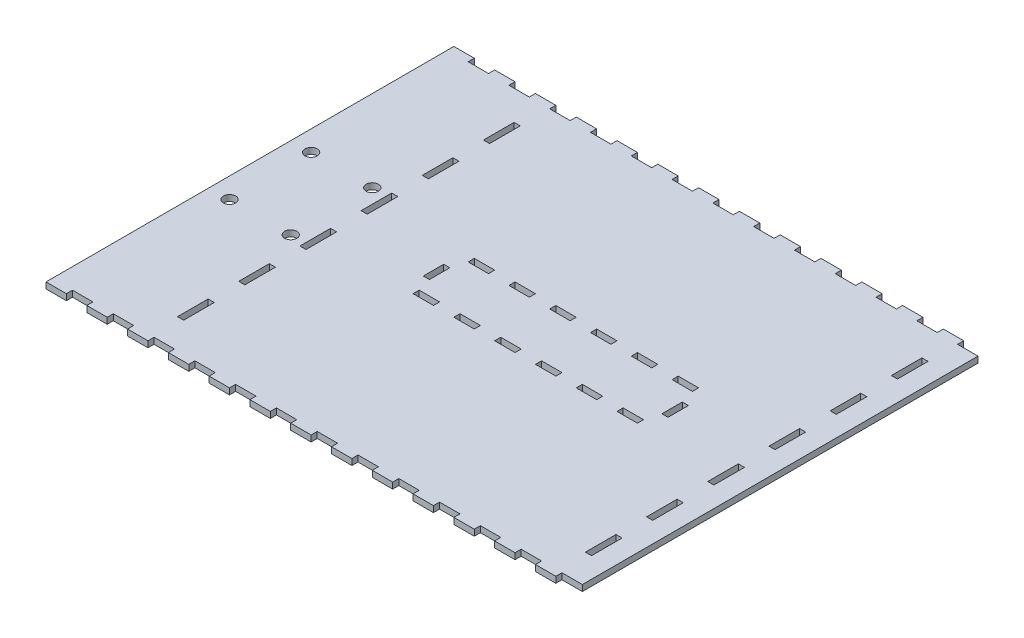
SolidWorks part; units mm, degrees
ref_plane "Front Plane" through (0, 0, 0) normal (0, 0, 1) x (1, 0, 0)
ref_plane "Top Plane" through (0, 0, 0) normal (0, 1, 0) x (1, 0, 0)
ref_plane "Right Plane" through (0, 0, 0) normal (1, 0, 0) x (0, 0, -1)
sketch "Sketch3" plane through (0, 0, 0) normal (0, 1, 0) x (1, 0, 0)
  line L0 (0, 0) -> (-300, 0) construction
  line L1 (-300, -97) -> (-300, 97)
  line L2 (-290, 100) -> (-300, 100)
  line L3 (-290, 97) -> (-290, 100)
  line L4 (-280, 97) -> (-290, 97)
  line L5 (-300, 100) -> (-300, 97)
  line L6 (-270, 100) -> (-280, 100)
  line L7 (-270, 97) -> (-270, 100)
  line L8 (-260, 97) -> (-270, 97)
  line L9 (-280, 100) -> (-280, 97)
  line L10 (-250, 100) -> (-260, 100)
  line L11 (-250, 97) -> (-250, 100)
  line L12 (-240, 97) -> (-250, 97)
  line L13 (-260, 100) -> (-260, 97)
  line L14 (-150, -100) -> (-150, 100) construction
  line L15 (-230, 100) -> (-240, 100)
  line L16 (-230, 97) -> (-230, 100)
  line L17 (-220, 97) -> (-230, 97)
  line L18 (-240, 100) -> (-240, 97)
  line L19 (-210, 100) -> (-220, 100)
  line L20 (-210, 97) -> (-210, 100)
  line L21 (-200, 97) -> (-210, 97)
  line L22 (-40, 97) -> (-40, -97)
  line L23 (-50, 37.5) -> (-53, 37.5)
  line L24 (-50, 7.5) -> (-53, 7.5)
  line L25 (-50, -45.947) -> (-50, 45.947) construction
  line L26 (-250, 37.5) -> (-253, 37.5)
  line L27 (-250, 7.5) -> (-253, 7.5)
  line L28 (-250, 48.5) -> (-250, -48.5) construction
  line L29 (-250, 48.5) -> (-223, 48.5) construction
  line L30 (-223, 48.5) -> (-223, -48.5) construction
  line L31 (-210, 15) -> (-90, 15) construction
  line L32 (-90, 15) -> (-90, 5) construction
  line L33 (-50, 7.5) -> (-50, 22.5)
  line L34 (-220, 100) -> (-220, 97)
  line L35 (-190, 100) -> (-200, 100)
  line L36 (-190, 97) -> (-190, 100)
  line L37 (-180, 97) -> (-190, 97)
  line L38 (-200, 100) -> (-200, 97)
  line L39 (-170, 100) -> (-180, 100)
  line L40 (-170, 97) -> (-170, 100)
  line L41 (-160, 97) -> (-170, 97)
  line L42 (-180, 100) -> (-180, 97)
  line L43 (-150, 100) -> (-160, 100)
  line L44 (-150, 97) -> (-150, 100)
  line L45 (-140, 97) -> (-150, 97)
  line L46 (-160, 100) -> (-160, 97)
  line L47 (-130, 100) -> (-140, 100)
  line L48 (-130, 97) -> (-130, 100)
  line L49 (-120, 97) -> (-130, 97)
  line L50 (-140, 100) -> (-140, 97)
  line L51 (-110, 100) -> (-120, 100)
  line L52 (-110, 97) -> (-110, 100)
  line L53 (-100, 97) -> (-110, 97)
  line L54 (-120, 100) -> (-120, 97)
  line L55 (-90, 100) -> (-100, 100)
  line L56 (-90, 97) -> (-90, 100)
  line L57 (-80, 97) -> (-90, 97)
  line L58 (-100, 100) -> (-100, 97)
  line L59 (-70, 100) -> (-80, 100)
  line L60 (-70, 97) -> (-70, 100)
  line L61 (-60, 97) -> (-70, 97)
  line L62 (-80, 100) -> (-80, 97)
  line L63 (-50, 100) -> (-60, 100)
  line L64 (-50, 97) -> (-50, 100)
  line L65 (-40, 97) -> (-50, 97)
  line L66 (-60, 100) -> (-60, 97)
  line L67 (-50, 22.5) -> (-53, 22.5)
  line L68 (-210, -15) -> (-90, -15) construction
  line L69 (-53, 7.5) -> (-53, 22.5)
  line L70 (-50, 37.5) -> (-50, 52.5)
  line L71 (-50, 52.5) -> (-53, 52.5)
  line L72 (-53, 37.5) -> (-53, 52.5)
  line L73 (-50, 67.5) -> (-53, 67.5)
  line L74 (-50, 67.5) -> (-50, 82.5)
  line L75 (-50, 82.5) -> (-53, 82.5)
  line L76 (-60, -100) -> (-60, -97)
  line L77 (-40, -97) -> (-50, -97)
  line L78 (-50, -97) -> (-50, -100)
  line L79 (-50, -100) -> (-60, -100)
  line L80 (-80, -100) -> (-80, -97)
  line L81 (-60, -97) -> (-70, -97)
  line L82 (-70, -97) -> (-70, -100)
  line L83 (-70, -100) -> (-80, -100)
  line L84 (-100, -100) -> (-100, -97)
  line L85 (-80, -97) -> (-90, -97)
  line L86 (-90, -97) -> (-90, -100)
  line L87 (-90, -100) -> (-100, -100)
  line L88 (-120, -100) -> (-120, -97)
  line L89 (-100, -97) -> (-110, -97)
  line L90 (-110, -97) -> (-110, -100)
  line L91 (-110, -100) -> (-120, -100)
  line L92 (-140, -100) -> (-140, -97)
  line L93 (-120, -97) -> (-130, -97)
  line L94 (-130, -97) -> (-130, -100)
  line L95 (-130, -100) -> (-140, -100)
  line L96 (-160, -100) -> (-160, -97)
  line L97 (-140, -97) -> (-150, -97)
  line L98 (-150, -97) -> (-150, -100)
  line L99 (-150, -100) -> (-160, -100)
  line L100 (-180, -100) -> (-180, -97)
  line L101 (-160, -97) -> (-170, -97)
  line L102 (-170, -97) -> (-170, -100)
  line L103 (-170, -100) -> (-180, -100)
  line L104 (-200, -100) -> (-200, -97)
  line L105 (-180, -97) -> (-190, -97)
  line L106 (-190, -97) -> (-190, -100)
  line L107 (-190, -100) -> (-200, -100)
  line L108 (-250, -48.5) -> (-223, -48.5) construction
  line L109 (-250, 7.5) -> (-250, 22.5)
  line L110 (-220, -100) -> (-220, -97)
  line L111 (-53, 67.5) -> (-53, 82.5)
  line L112 (-53, -67.5) -> (-53, -82.5)
  line L113 (-50, -82.5) -> (-53, -82.5)
  line L114 (-200, -97) -> (-210, -97)
  line L115 (-210, -97) -> (-210, -100)
  line L116 (-210, -100) -> (-220, -100)
  line L117 (-240, -100) -> (-240, -97)
  line L118 (-220, -97) -> (-230, -97)
  line L119 (-230, -97) -> (-230, -100)
  line L120 (-230, -100) -> (-240, -100)
  line L121 (-50, -67.5) -> (-50, -82.5)
  line L122 (-260, -100) -> (-260, -97)
  line L123 (-240, -97) -> (-250, -97)
  line L124 (-250, -97) -> (-250, -100)
  line L125 (-250, -100) -> (-260, -100)
  line L126 (-280, -100) -> (-280, -97)
  line L127 (-260, -97) -> (-270, -97)
  line L128 (-270, -97) -> (-270, -100)
  line L129 (-270, -100) -> (-280, -100)
  line L130 (-300, -100) -> (-300, -97)
  line L131 (-210, 15) -> (-210, -15) construction
  line L132 (-115, 15) -> (-125, 15)
  line L133 (-90, 5) -> (-93, 5)
  line L134 (-90, 5) -> (-90, -5)
  line L135 (-90, -5) -> (-93, -5)
  line L136 (-93, 5) -> (-93, -5)
  line L137 (-95, 15) -> (-105, 15)
  line L138 (-95, 15) -> (-95, 12)
  line L139 (-95, 12) -> (-105, 12)
  line L140 (-105, 15) -> (-105, 12)
  line L141 (-115, 12) -> (-125, 12)
  line L142 (-125, 15) -> (-125, 12)
  line L143 (-135, 15) -> (-145, 15)
  line L144 (-135, 12) -> (-145, 12)
  line L145 (-145, 15) -> (-145, 12)
  line L146 (-155, 15) -> (-165, 15)
  line L147 (-155, 12) -> (-165, 12)
  line L148 (-165, 15) -> (-165, 12)
  line L149 (-175, 15) -> (-185, 15)
  line L150 (-175, 12) -> (-185, 12)
  line L151 (-185, 15) -> (-185, 12)
  line L152 (-195, 15) -> (-205, 15)
  line L153 (-195, 12) -> (-205, 12)
  line L154 (-205, 15) -> (-205, 12)
  line L155 (-195, 12) -> (-195, 15)
  line L156 (-175, 12) -> (-175, 15)
  line L157 (-155, 12) -> (-155, 15)
  line L158 (-135, 12) -> (-135, 15)
  line L159 (-115, 12) -> (-115, 15)
  line L160 (-207, 5) -> (-207, -5)
  line L161 (-210, -5) -> (-207, -5)
  line L162 (-210, 5) -> (-210, -5)
  line L163 (-210, 5) -> (-207, 5)
  line L164 (-115, -12) -> (-115, -15)
  line L165 (-135, -12) -> (-135, -15)
  line L166 (-155, -12) -> (-155, -15)
  line L167 (-175, -12) -> (-175, -15)
  line L168 (-195, -12) -> (-195, -15)
  line L169 (-205, -15) -> (-205, -12)
  line L170 (-195, -12) -> (-205, -12)
  line L171 (-195, -15) -> (-205, -15)
  line L172 (-185, -15) -> (-185, -12)
  line L173 (-175, -12) -> (-185, -12)
  line L174 (-175, -15) -> (-185, -15)
  line L175 (-165, -15) -> (-165, -12)
  line L176 (-155, -12) -> (-165, -12)
  line L177 (-155, -15) -> (-165, -15)
  line L178 (-145, -15) -> (-145, -12)
  line L179 (-135, -12) -> (-145, -12)
  line L180 (-135, -15) -> (-145, -15)
  line L181 (-125, -15) -> (-125, -12)
  line L182 (-115, -12) -> (-125, -12)
  line L183 (-105, -15) -> (-105, -12)
  line L184 (-95, -12) -> (-105, -12)
  line L185 (-95, -15) -> (-95, -12)
  line L186 (-95, -15) -> (-105, -15)
  line L187 (-115, -15) -> (-125, -15)
  line L188 (-250, 22.5) -> (-253, 22.5)
  line L189 (-253, 7.5) -> (-253, 22.5)
  line L190 (-250, 37.5) -> (-250, 52.5)
  line L191 (-250, 52.5) -> (-253, 52.5)
  line L192 (-253, 37.5) -> (-253, 52.5)
  line L193 (-250, 67.5) -> (-253, 67.5)
  line L194 (-250, 67.5) -> (-250, 82.5)
  line L195 (-250, 82.5) -> (-253, 82.5)
  line L196 (-253, 67.5) -> (-253, 82.5)
  line L197 (-253, -67.5) -> (-253, -82.5)
  line L198 (-250, -82.5) -> (-253, -82.5)
  line L199 (-250, -67.5) -> (-250, -82.5)
  line L200 (-250, -67.5) -> (-253, -67.5)
  line L201 (-253, -37.5) -> (-253, -52.5)
  line L202 (-250, -52.5) -> (-253, -52.5)
  line L203 (-250, -37.5) -> (-250, -52.5)
  line L204 (-253, -7.5) -> (-253, -22.5)
  line L205 (-250, -22.5) -> (-253, -22.5)
  line L206 (-250, -7.5) -> (-250, -22.5)
  line L207 (-250, -7.5) -> (-253, -7.5)
  line L208 (-250, -37.5) -> (-253, -37.5)
  line L209 (-50, -67.5) -> (-53, -67.5)
  line L210 (-53, -37.5) -> (-53, -52.5)
  line L211 (-50, -52.5) -> (-53, -52.5)
  line L212 (-50, -37.5) -> (-50, -52.5)
  line L213 (-53, -7.5) -> (-53, -22.5)
  line L214 (-50, -22.5) -> (-53, -22.5)
  line L215 (-50, -7.5) -> (-50, -22.5)
  line L216 (-50, -7.5) -> (-53, -7.5)
  line L217 (-50, -37.5) -> (-53, -37.5)
  line L231 (-280, -97) -> (-290, -97)
  line L232 (-290, -97) -> (-290, -100)
  line L233 (-290, -100) -> (-300, -100)
  circle A0 centre (-290, 20) radius 3
  circle A1 centre (-260, 20) radius 3
  circle A2 centre (-260, -20) radius 3
  circle A3 centre (-290, -20) radius 3
  point P31 (-250, 36)
  point P80 (-91.5, 0)
  point P82 (-150, 0)
  point P126 (-223, 0)
  point P128 (-250, 18)
  point P129 (-50, 0)
  point P150 (-150, -15)
  point P151 (-150, 15)
  point P183 (-208.5, 0)
  point P212 (-223, 18)
  point P218 (-223, 36)
  dimension "D17" = 6
  dimension "D18" = 6
  dimension "D1" = 300
  dimension "D4" = 7.5
  dimension "D5" = 100
  dimension "D6" = 97
  dimension "D7" = 15
  dimension "D8" = 97
  dimension "D9" = 3
  dimension "D10" = 3
  dimension "D11" = 48.5
  dimension "D12" = 27
  dimension "D13" = 60
  dimension "D14" = 15
  dimension "D15" = 30
  dimension "D16" = 20
  dimension "D19" = 194
  dimension "D20" = 10
  dimension "D21" = 3
  dimension "D22" = 7.5
  dimension "D23" = 15
  dimension "D24" = 3
  dimension "D25" = 3
  dimension "D29" = 10
  dimension "D30" = 3
  dimension "D31" = 10
  dimension "D32" = 3
  dimension "D33" = 10
  dimension "D34" = 5
  dimension "D35" = 6
  dimension "D36" = 3
extrude "Boss-Extrude1" add sketch "Sketch3" along normal blind 3 contours L1 L116 L115 L107 L106 L83 L82 L79 L95 L98 L99 L91 L90 L86 region at (-170.2077, 0, 0)
sketch "Sketch4" plane through (0, 3, 0) normal (0, 1, 0) x (1, 0, 0)
  line L0 (-53, 5) -> (-53, 15) construction
  line L1 (-53, 46) -> (-77, 46)
  line L2 (-53, 46) -> (-53, -46)
  line L3 (-53, -46) -> (-77, -46)
  line L4 (-77, 46) -> (-77, -46)
  line L5 (-90, 0) -> (0, 0) construction
  line L6 (-90, 5) -> (-90, -5) construction
  dimension "D1" = 92
  dimension "D2" = 24
  dimension "D3" = 46
